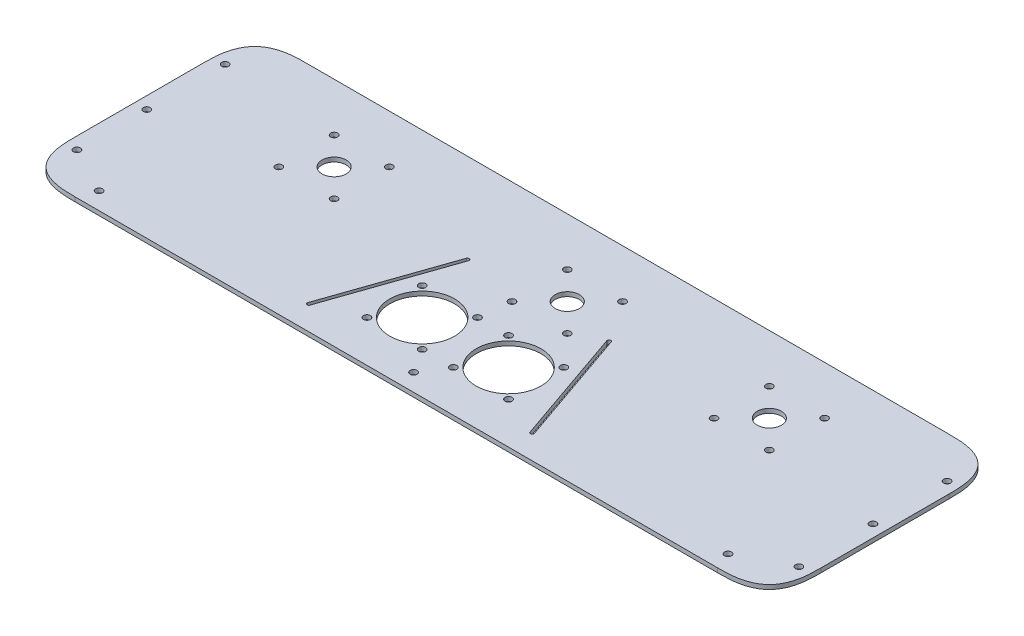
SolidWorks part; units mm, degrees
ref_plane "Front Plane" through (0, 0, 0) normal (0, 0, 1) x (1, 0, 0)
ref_plane "Top Plane" through (0, 0, 0) normal (0, 1, 0) x (1, 0, 0)
ref_plane "Right Plane" through (0, 0, 0) normal (1, 0, 0) x (0, 0, -1)
sketch "Sketch1" plane through (0, 0, 0) normal (0, 1, 0) x (1, 0, 0)
  line L1 (-103.134, 171.9149) -> (328.866, 171.9149)
  line L2 (-103.134, 171.9149) -> (-103.134, -28.0851)
  line L3 (-103.134, -28.0851) -> (328.866, -28.0851)
  line L4 (328.866, 171.9149) -> (328.866, -28.0851)
extrude "Boss-Extrude1" add sketch "Sketch1" along normal blind 2.5 contours L1 L4 L3 L2
sketch "Sketch3" plane through (0, 2.5, 0) normal (0, 1, 0) x (1, 0, 0)
  line L0 (-13.134, 71.9149) -> (-29.1359, 55.9131)
  line L1 (2.8678, 87.9167) -> (-29.1359, 87.9167)
  line L2 (2.8678, 87.9167) -> (2.8678, 55.9131)
  line L3 (2.8678, 55.9131) -> (-29.1359, 55.9131)
  line L4 (-29.1359, 87.9167) -> (-29.1359, 55.9131)
  line L5 (2.8678, 87.9167) -> (-29.1359, 55.9131) construction
  line L6 (2.8678, 55.9131) -> (-29.1359, 87.9167) construction
  line L7 (-103.134, 71.9149) -> (-13.134, 71.9149)
  line L8 (-103.134, 171.9149) -> (-103.134, -28.0851) construction
  line L9 (238.866, 71.9149) -> (238.866, 115.9149)
  line L14 (62.253, -0.3819) -> (46.2512, -16.3837)
  line L15 (238.866, 115.9149) -> (328.866, 115.9149)
  line L18 (328.866, 171.9149) -> (328.866, -28.0851) construction
  line L19 (238.866, 71.9149) -> (222.8641, 55.9131)
  line L20 (254.8678, 87.9167) -> (222.8641, 87.9167)
  line L21 (254.8678, 87.9167) -> (254.8678, 55.9131)
  line L22 (254.8678, 55.9131) -> (222.8641, 55.9131)
  line L23 (222.8641, 87.9167) -> (222.8641, 55.9131)
  line L24 (254.8678, 87.9167) -> (222.8641, 55.9131) construction
  line L25 (254.8678, 55.9131) -> (222.8641, 87.9167) construction
  line L27 (328.866, 71.9149) -> (238.866, 71.9149)
  line L28 (238.866, 115.9149) -> (238.866, 171.9149)
  line L29 (238.866, 171.9149) -> (328.866, 171.9149)
  line L30 (328.866, 115.9149) -> (328.866, 171.9149)
  line L31 (328.866, 115.9149) -> (-169.3435, 115.9149)
  line L32 (328.866, 115.9149) -> (328.866, 173.2785)
  line L33 (328.866, 173.2785) -> (-169.3435, 173.2785)
  line L34 (-169.3435, 115.9149) -> (-169.3435, 173.2785)
  line L35 (78.2549, 15.6199) -> (46.2512, 15.6199)
  line L36 (78.2549, 15.6199) -> (78.2549, -16.3837)
  line L37 (78.2549, -16.3837) -> (46.2512, -16.3837)
  line L38 (46.2512, 15.6199) -> (46.2512, -16.3837)
  line L39 (78.2549, 15.6199) -> (46.2512, -16.3837) construction
  line L40 (78.2549, -16.3837) -> (46.2512, 15.6199) construction
  circle A0 centre (-13.134, 71.9149) radius 7
  circle A1 centre (-29.1359, 55.9131) radius 2
  circle A2 centre (-29.1359, 87.9167) radius 2
  circle A3 centre (2.8678, 87.9167) radius 2
  circle A4 centre (2.8678, 55.9131) radius 2
  circle A10 centre (238.866, 71.9149) radius 7
  circle A11 centre (222.8641, 55.9131) radius 2
  circle A12 centre (222.8641, 87.9167) radius 2
  circle A13 centre (254.8678, 87.9167) radius 2
  circle A14 centre (254.8678, 55.9131) radius 2
  circle A15 centre (62.253, -0.3819) radius 7
  circle A16 centre (46.2512, -16.3837) radius 2
  circle A17 centre (46.2512, 15.6199) radius 2
  circle A18 centre (78.2549, 15.6199) radius 2
  circle A19 centre (78.2549, -16.3837) radius 2
  point P10 (328.866, 71.9149)
extrude "Cut-Extrude1" cut sketch "Sketch3" against normal blind 2.5 contours A2 | A3 | A4 | A1 | A0 | A11 | A14 | A13 | A10 | A12 | L32 L31 L34 L33
sketch "Sketch5" plane through (0, 2.5, 0) normal (0, 1, 0) x (1, 0, 0)
  line L0 (263.7413, -28.0851) -> (263.7413, -18.0851)
  line L3 (-103.134, -28.0851) -> (328.866, -28.0851) construction
  line L5 (263.7413, -18.0851) -> (328.866, -18.0851)
  line L6 (263.7413, -18.0851) -> (263.7413, -28.0851)
  line L7 (263.7413, -28.0851) -> (328.866, -28.0851)
  line L8 (328.866, -18.0851) -> (328.866, -28.0851)
  line L9 (263.7413, -18.0851) -> (-103.134, -18.0851)
  line L10 (263.7413, -18.0851) -> (263.7413, -28.0851)
  line L11 (263.7413, -28.0851) -> (-103.134, -28.0851)
  line L12 (-103.134, -18.0851) -> (-103.134, -28.0851)
  line M12 (328.866, -28.0851) -> (328.866, 115.9149)
  line M14 (-103.134, 115.9149) -> (-103.134, -28.0851)
  line M15 (-103.134, -28.0851) -> (328.866, -28.0851)
extrude "Cut-Extrude3" cut sketch "Sketch5" against normal blind 2.5 contours L0 L9 M14 M15 | L5 L0 M15 M12 region at (80.3036, 2.5, 23.0851) region at (296.3036, 2.5, 23.0851)
sketch "Sketch6" plane through (0, 2.5, 0) normal (0, 1, 0) x (1, 0, 0)
  line L0 (328.866, -18.0851) -> (-103.134, -18.0851) construction
  line L1 (112.866, -18.0851) -> (112.866, 21.9149)
  line L2 (112.866, 21.9149) -> (137.866, 21.9149)
  line L3 (112.866, 21.9149) -> (87.866, 21.9149)
  line L4 (87.866, 21.9149) -> (71.8641, 5.9131)
  line L5 (103.8678, 37.9167) -> (71.8641, 37.9167)
  line L6 (103.8678, 37.9167) -> (103.8678, 5.9131)
  line L7 (103.8678, 5.9131) -> (71.8641, 5.9131)
  line L8 (71.8641, 37.9167) -> (71.8641, 5.9131)
  line L9 (103.8678, 37.9167) -> (71.8641, 5.9131) construction
  line L10 (103.8678, 5.9131) -> (71.8641, 37.9167) construction
  line L11 (137.866, 21.9149) -> (121.8641, 5.9131)
  line L12 (153.8678, 37.9167) -> (121.8641, 37.9167)
  line L13 (153.8678, 37.9167) -> (153.8678, 5.9131)
  line L14 (153.8678, 5.9131) -> (121.8641, 5.9131)
  line L15 (121.8641, 37.9167) -> (121.8641, 5.9131)
  line L16 (153.8678, 37.9167) -> (121.8641, 5.9131) construction
  line L17 (153.8678, 5.9131) -> (121.8641, 37.9167) construction
  circle A0 centre (137.866, 21.9149) radius 18.75
  circle A1 centre (87.866, 21.9149) radius 18.75
  circle A2 centre (87.866, 21.9149) radius 7
  circle A3 centre (71.8641, 5.9131) radius 2
  circle A4 centre (71.8641, 37.9167) radius 2
  circle A5 centre (103.8678, 37.9167) radius 2
  circle A6 centre (103.8678, 5.9131) radius 2
  circle A7 centre (137.866, 21.9149) radius 7
  circle A8 centre (121.8641, 5.9131) radius 2
  circle A9 centre (121.8641, 37.9167) radius 2
  circle A10 centre (153.8678, 37.9167) radius 2
  circle A11 centre (153.8678, 5.9131) radius 2
  point P0 (112.866, -18.0851)
extrude "Cut-Extrude4" cut sketch "Sketch6" against normal blind 2.5 contours A11 | A8 | A10 | A9 | A5 | A6 | A3 | A4
sketch "Sketch8" plane through (0, 2.5, 0) normal (0, 1, 0) x (1, 0, 0)
  line L2 (153.8678, 5.9131) -> (153.8678, 90.0973)
  line L3 (153.8678, 90.0973) -> (71.8641, 90.0973)
  line L4 (71.8641, 90.0973) -> (71.8641, 5.9131)
  line L5 (153.8678, 64.0929) -> (71.8641, 64.0929)
  line L10 (177.527, -4.0851) -> (153.8678, 64.0929) construction
  line L14 (176.5823, -4.4129) -> (152.9231, 63.7651)
  line L15 (178.4718, -3.7572) -> (154.8125, 64.4208)
  line L16 (48.2049, -4.0851) -> (71.8641, 64.0929) construction
  line L17 (47.2602, -3.7572) -> (70.9194, 64.4208)
  line L18 (49.1496, -4.4129) -> (72.8089, 63.7651)
  arc A6 (176.5823, -4.4129) -> (178.4718, -3.7572) centre (177.527, -4.0851) ccw
  arc A7 (154.8125, 64.4208) -> (152.9231, 63.7651) centre (153.8678, 64.0929) ccw
  arc A8 (47.2602, -3.7572) -> (49.1496, -4.4129) centre (48.2049, -4.0851) ccw
  arc A9 (72.8089, 63.7651) -> (70.9194, 64.4208) centre (71.8641, 64.0929) ccw
  point P17 (177.527, 5.9131)
  point P18 (48.2049, 5.9131)
  point P19 (165.6974, 30.0039)
  point P22 (112.866, -4.0851)
  point P27 (60.0345, 30.0039)
extrude "Cut-Extrude5" cut sketch "Sketch8" against normal blind 2.5 contours L17 A9 L18 A8 | L15 A7 L14 A6
fillet "Fillet1" radius 30 4 edges at (-103.134, 1.25, -115.9149) (-103.134, 1.25, 18.0851) (328.866, 1.25, -115.9149) (328.866, 1.25, 18.0851) curvature continuous yes
sketch "Sketch9" plane through (0, 2.5, 0) normal (0, 1, 0) x (1, 0, 0)
  line L0 (328.866, 62.6221) -> (321.866, 62.6221)
  line L1 (328.866, 85.9149) -> (328.866, 11.9149) construction
  line L2 (321.866, 109.7214) -> (321.866, -11.8915)
  line L3 (321.866, 6.0103) -> (321.866, -11.8915)
  line L4 (321.866, 109.7214) -> (321.866, 91.8196)
  line L5 (321.866, 91.8196) -> (321.866, 109.7214)
  line L6 (-103.134, 46.4673) -> (-96.134, 46.4673)
  line L7 (-103.134, 85.9149) -> (-103.134, 11.9149) construction
  line L8 (-96.134, 46.4673) -> (-96.134, 109.7214)
  line L9 (-96.134, 109.7214) -> (-96.134, -11.8916)
  line L10 (-96.134, -11.8916) -> (-96.134, 6.0103)
  line L11 (-96.134, 109.7214) -> (-96.134, 97.3154)
  line L12 (-96.134, 109.7214) -> (-96.134, 91.8196)
  circle A0 centre (321.866, 6.0103) radius 2
  circle A1 centre (321.866, 48.9149) radius 2
  circle A2 centre (321.866, 91.8196) radius 2
  circle A3 centre (-96.134, 46.4673) radius 2
  circle A4 centre (-96.134, 91.8196) radius 2
  circle A5 centre (-96.134, 6.0103) radius 2
  spline S0 degree 2 poles (328.866, 85.9149) (328.866, 87.9765) (328.8467, 89.0459) (328.8162, 90.7467) (328.7231, 92.1742) (328.5043, 95.5283) (327.8783, 98.3317) (326.3274, 105.2776) (322.2688, 109.3319) (318.2198, 113.3765) (311.2895, 114.9258) (308.4764, 115.5546) (305.1048, 115.7733) (303.6844, 115.8655) (301.9893, 115.8958) (300.9233, 115.9149) (298.866, 115.9149) knots 0 0 0 0.0625 0.0625 0.125 0.125 0.25 0.25 0.5 0.5 0.75 0.75 0.875 0.875 0.9375 0.9375 1 1 1 construction
  spline S1 degree 2 poles (298.866, -18.0851) (300.9275, -18.0851) (301.997, -18.0659) (303.6978, -18.0353) (305.1253, -17.9422) (308.4794, -17.7234) (311.2827, -17.0975) (318.2287, -15.5466) (322.283, -11.4879) (326.3276, -7.4389) (327.8768, -0.5086) (328.5057, 2.3045) (328.7244, 5.6761) (328.8165, 7.0965) (328.8469, 8.7916) (328.866, 9.8575) (328.866, 11.9149) knots 0 0 0 0.0625 0.0625 0.125 0.125 0.25 0.25 0.5 0.5 0.75 0.75 0.875 0.875 0.9375 0.9375 1 1 1 construction
  spline S2 degree 2 poles (-73.134, 115.9149) (-75.1956, 115.9149) (-76.2651, 115.8957) (-77.9658, 115.8651) (-79.3933, 115.772) (-82.7474, 115.5532) (-85.5508, 114.9273) (-92.4967, 113.3764) (-96.551, 109.3177) (-100.5957, 105.2687) (-102.1449, 98.3384) (-102.7737, 95.5254) (-102.9924, 92.1538) (-103.0846, 90.7333) (-103.1149, 89.0383) (-103.134, 87.9723) (-103.134, 85.9149) knots 0 0 0 0.0625 0.0625 0.125 0.125 0.25 0.25 0.5 0.5 0.75 0.75 0.875 0.875 0.9375 0.9375 1 1 1 construction
  spline S3 degree 2 poles (-103.134, 11.9149) (-103.134, 9.8534) (-103.1148, 8.7839) (-103.0842, 7.0831) (-102.9911, 5.6556) (-102.7723, 2.3015) (-102.1464, -0.5019) (-100.5955, -7.4478) (-96.5368, -11.5021) (-92.4879, -15.5467) (-85.5575, -17.0959) (-82.7445, -17.7248) (-79.3729, -17.9435) (-77.9525, -18.0356) (-76.2574, -18.066) (-75.1914, -18.0851) (-73.134, -18.0851) knots 0 0 0 0.0625 0.0625 0.125 0.125 0.25 0.25 0.5 0.5 0.75 0.75 0.875 0.875 0.9375 0.9375 1 1 1 construction
extrude "Cut-Extrude6" cut sketch "Sketch9" against normal blind 2.5 contours A0 | A1 | A2 | A5 | A3 | A4
sketch "Sketch10" plane through (0, 2.5, 0) normal (0, 1, 0) x (1, 0, 0)
  line L0 (232.1904, -18.0851) -> (232.1904, -8.0851)
  line L1 (298.866, -18.0851) -> (-73.134, -18.0851) construction
  line L2 (324.9418, -8.0851) -> (-99.2097, -8.0851)
  line L3 (324.9418, -8.0851) -> (232.1904, -8.0851)
  line L4 (324.9418, -8.0851) -> (232.1904, -8.0851)
  line L5 (324.9418, -8.0851) -> (232.1904, -8.0851)
  line L6 (324.9418, -8.0851) -> (294.9418, -8.0851)
  line L7 (-99.2097, -8.0851) -> (-78.7572, -8.0851)
  line L8 (-99.2097, -8.0851) -> (-69.2097, -8.0851)
  circle A0 centre (112.866, -8.0851) radius 2
  circle A3 centre (294.9418, -8.0851) radius 2
  circle A4 centre (-69.2097, -8.0851) radius 2
  spline S0 degree 2 poles (298.866, -18.0851) (300.9275, -18.0851) (301.997, -18.0659) (303.6978, -18.0353) (305.1253, -17.9422) (308.4794, -17.7234) (311.2827, -17.0975) (318.2287, -15.5466) (322.283, -11.4879) (326.3276, -7.4389) (327.8768, -0.5086) (328.5057, 2.3045) (328.7244, 5.6761) (328.8165, 7.0965) (328.8469, 8.7916) (328.866, 9.8575) (328.866, 11.9149) knots 0 0 0 0.0625 0.0625 0.125 0.125 0.25 0.25 0.5 0.5 0.75 0.75 0.875 0.875 0.9375 0.9375 1 1 1 construction
  spline S1 degree 2 poles (-103.134, 11.9149) (-103.134, 9.8534) (-103.1148, 8.7839) (-103.0842, 7.0831) (-102.9911, 5.6556) (-102.7723, 2.3015) (-102.1464, -0.5019) (-100.5955, -7.4478) (-96.5368, -11.5021) (-92.4879, -15.5467) (-85.5575, -17.0959) (-82.7445, -17.7248) (-79.3729, -17.9435) (-77.9525, -18.0356) (-76.2574, -18.066) (-75.1914, -18.0851) (-73.134, -18.0851) knots 0 0 0 0.0625 0.0625 0.125 0.125 0.25 0.25 0.5 0.5 0.75 0.75 0.875 0.875 0.9375 0.9375 1 1 1 construction
extrude "Cut-Extrude7" cut sketch "Sketch10" against normal blind 2.5 contours A4 | A0 | A3
extrude "Cut-Extrude8" cut sketch "Sketch6<3>" against normal blind 10 contours A1 | A0
sketch "Sketch6<3>" plane through (0, 2.5, 0) normal (0, 1, 0) x (1, 0, 0) same geometry as "Sketch6"
sketch "Sketch12" plane through (0, 2.5, 0) normal (0, 1, 0) x (1, 0, 0)
  line L0 (121.8641, 37.9167) -> (121.8641, 71.9149)
  line L1 (238.866, 71.9149) -> (-13.134, 71.9149)
  line L3 (121.8641, 71.9149) -> (105.8623, 55.9131)
  line L4 (137.866, 87.9167) -> (105.8623, 87.9167)
  line L5 (137.866, 87.9167) -> (137.866, 55.9131)
  line L6 (137.866, 55.9131) -> (105.8623, 55.9131)
  line L7 (105.8623, 87.9167) -> (105.8623, 55.9131)
  line L8 (137.866, 87.9167) -> (105.8623, 55.9131) construction
  line L9 (137.866, 55.9131) -> (105.8623, 87.9167) construction
  circle A1 centre (121.8641, 71.9149) radius 7
  circle A2 centre (105.8623, 55.9131) radius 2
  circle A3 centre (105.8623, 87.9167) radius 2
  circle A4 centre (137.866, 87.9167) radius 2
  circle A5 centre (137.866, 55.9131) radius 2
  point P7 (121.8641, 71.067)
extrude "Cut-Extrude9" cut sketch "Sketch12" against normal blind 10 contours A5 | A4 | A3 | A2 | A1
